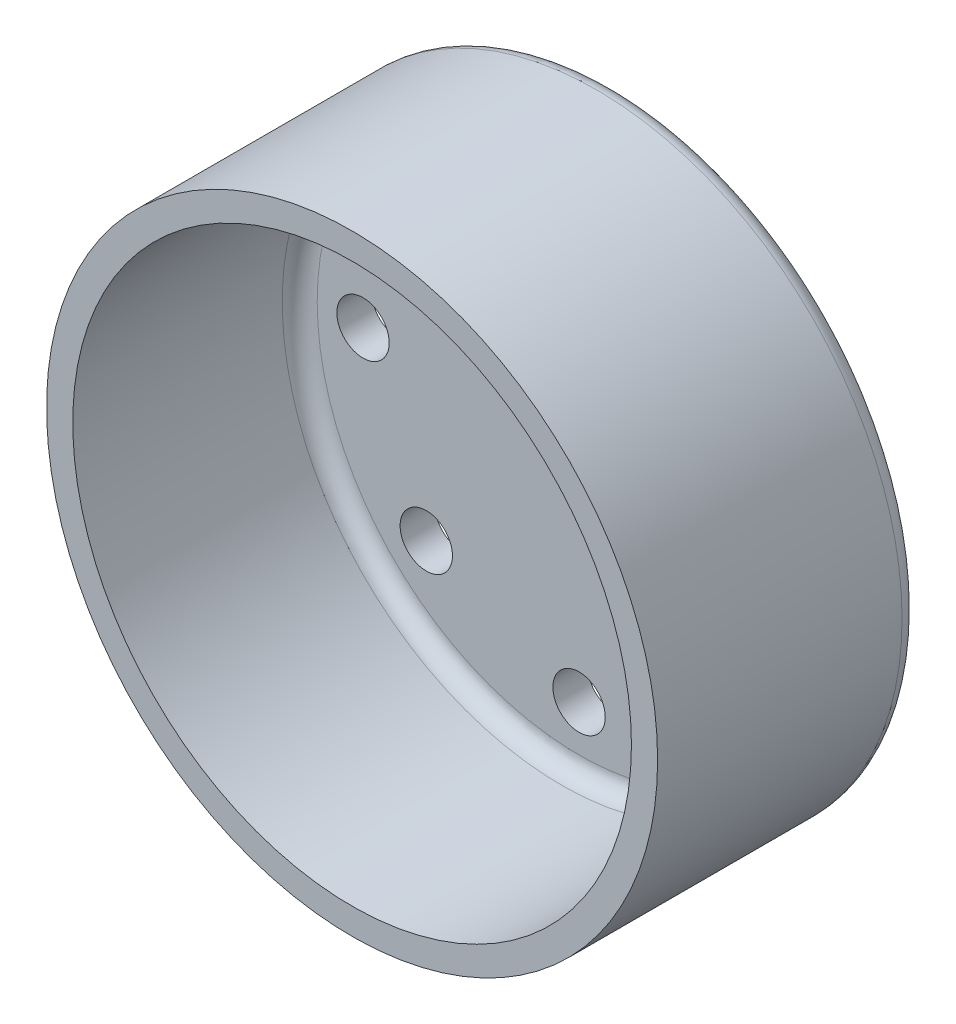
SolidWorks part; units mm, degrees
ref_plane "Front Plane" through (0, 0, 0) normal (0, 0, 1) x (1, 0, 0)
ref_plane "Top Plane" through (0, 0, 0) normal (0, 1, 0) x (1, 0, 0)
ref_plane "Right Plane" through (0, 0, 0) normal (1, 0, 0) x (0, 0, -1)
sketch "Sketch1" plane through (0, 0, 0) normal (0, 0, 1) x (1, 0, 0)
  circle A0 centre (0, 0) radius 35
  point P3 (0, 0)
  dimension "D1" = 70
extrude "Boss-Extrude1" add sketch "Sketch1" along normal blind 30
sketch "Sketch3" plane through (0, 0, 0) normal (0, 0, -1) x (-1, 0, 0)
  line L0 (0, 0) -> (0, -35)
  line L1 (0, -35) -> (35, 0)
  line L2 (35, 0) -> (-35, 0)
  line L3 (-35, 0) -> (0, 35)
  line L4 (0, 35) -> (0, 0)
  line L5 (0, -35) -> (-35, 0)
  circle A0 centre (0, 0) radius 35 construction
  circle A1 centre (24.75, 0) radius 3
  circle A2 centre (17.5, -17.5) radius 3
  circle A3 centre (0, -24.75) radius 3
  circle A4 centre (-24.75, 0) radius 3
  circle A5 centre (-17.5, -17.5) radius 3
  point P19 (0, 0)
  point P20 (0, 0)
  dimension "D4" = 6
  dimension "D5" = 6
  dimension "D6" = 6
  dimension "D7" = 6
  dimension "D8" = 6
  dimension "D1" = 24.75
  dimension "D2" = 24.75
  dimension "D3" = 24.75
extrude "Cut-Extrude1" cut sketch "Sketch3" against normal blind 60 contours L2 A1 | L1 A2 | L5 A5 | L5 A5 | A1 | A2 region at (-24.75, -1.2732, 0) region at (16.5997, -16.5997, 0) region at (18.4003, -18.4003, 0) region at (-16.5997, -16.5997, 0)
sketch "Sketch4" plane through (0, 0, 0) normal (0, 0, -1) x (-1, 0, 0)
extrude "Cut-Extrude2" cut sketch "Sketch3<3>" against normal blind 60 contours L0 A3 | L0 A3 | L2 A4 | L2 A4 region at (-1.2732, -24.75, 0) region at (1.2732, -24.75, 0) region at (24.75, -1.2732, 0) region at (24.75, 1.2732, 0)
sketch "Sketch3<3>" plane through (0, 0, 0) normal (0, 0, -1) x (-1, 0, 0) same geometry as "Sketch3"
sketch "Sketch5" plane through (0, 0, 30) normal (0, 0, 1) x (1, 0, 0)
  circle A0 centre (0, 0) radius 32
  dimension "D1" = 64
extrude "Cut-Extrude3" cut sketch "Sketch5" against normal blind 26
fillet "Fillet3" radius 2 1 edges at (35, 0, 0)
fillet "Fillet4" radius 2 1 edges at (32, 0, 4)
